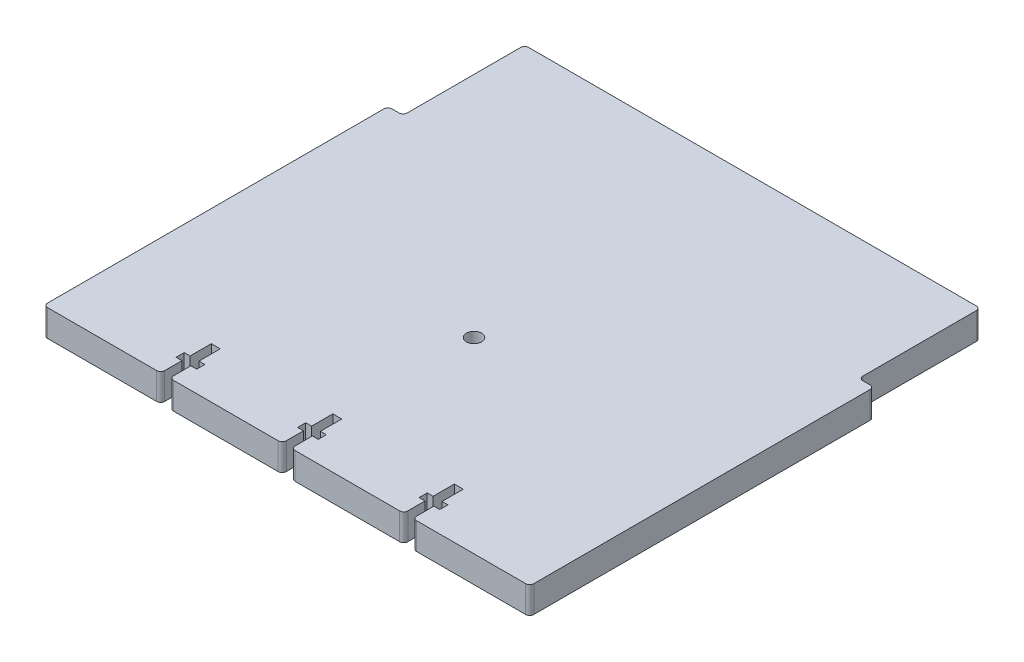
SolidWorks part; units mm, degrees
ref_plane "Front Plane" through (0, 0, 0) normal (0, 0, 1) x (1, 0, 0)
ref_plane "Top Plane" through (0, 0, 0) normal (0, 1, 0) x (1, 0, 0)
ref_plane "Right Plane" through (0, 0, 0) normal (1, 0, 0) x (0, 0, -1)
sketch "Sketch1" plane through (0, 0, 0) normal (0, 1, 0) x (1, 0, 0)
  line L1 (0, 0) -> (142.875, 0)
  line L2 (0, 107.95) -> (0, 146.05)
  line L3 (0, 146.05) -> (142.875, 146.05)
  line L4 (142.875, 107.95) -> (142.875, 146.05)
  line L5 (142.875, 0) -> (147.6375, 0)
  line L7 (142.875, 107.95) -> (147.6375, 107.95)
  line L8 (147.6375, 0) -> (147.6375, 107.95)
  line L9 (0, 0) -> (-4.7625, 0)
  line L11 (0, 107.95) -> (-4.7625, 107.95)
  line L12 (-4.7625, 0) -> (-4.7625, 107.95)
  dimension "D1" = 142.875
  dimension "D2" = 146.05
  dimension "D3" = 4.7625
  dimension "D4" = 4.7625
  dimension "D5" = 107.95
  dimension "D6" = 107.95
extrude "Boss-Extrude1" add sketch "Sketch1" along normal blind 8.382
sketch "Sketch10" plane through (0, 8.382, 0) normal (0, 1, 0) x (1, 0, 0)
  line L0 (71.4375, 146.05) -> (71.4375, 15.875) construction
  line L1 (70.0405, 9.2075) -> (68.199, 9.2075)
  line L2 (108.1405, 15.875) -> (110.9345, 15.875)
  line L3 (142.875, 146.05) -> (0, 146.05) construction
  line L4 (-4.7625, 0) -> (147.6375, 0) construction
  line L5 (70.0405, 6.6675) -> (70.0405, 0)
  line L6 (70.0405, 15.875) -> (72.8345, 15.875)
  line L7 (70.0405, 15.875) -> (70.0405, 9.2075)
  line L8 (70.0405, 0) -> (72.8345, 0)
  line L9 (72.8345, 15.875) -> (72.8345, 9.2075)
  line L10 (108.1405, 15.875) -> (108.1405, 9.2075)
  line L11 (110.9345, 15.875) -> (110.9345, 9.2075)
  line L12 (74.676, 6.6675) -> (72.8345, 6.6675)
  line L13 (74.676, 6.6675) -> (74.676, 9.2075)
  line L14 (74.676, 9.2075) -> (72.8345, 9.2075)
  line L15 (68.199, 6.6675) -> (68.199, 9.2075)
  line L16 (112.776, 9.2075) -> (110.9345, 9.2075)
  line L17 (112.776, 6.6675) -> (112.776, 9.2075)
  line L18 (70.0405, 6.6675) -> (68.199, 6.6675)
  line L19 (112.776, 6.6675) -> (110.9345, 6.6675)
  line L20 (110.9345, 6.6675) -> (110.9345, 0)
  line L21 (108.1405, 0) -> (110.9345, 0)
  line L22 (108.1405, 6.6675) -> (108.1405, 0)
  line L23 (108.1405, 6.6675) -> (106.299, 6.6675)
  line L24 (106.299, 6.6675) -> (106.299, 9.2075)
  line L25 (108.1405, 9.2075) -> (106.299, 9.2075)
  line L26 (72.8345, 6.6675) -> (72.8345, 0)
  line L27 (34.7345, 15.875) -> (34.7345, 9.2075)
  line L28 (31.9405, 15.875) -> (34.7345, 15.875)
  line L29 (31.9405, 15.875) -> (31.9405, 9.2075)
  line L30 (31.9405, 9.2075) -> (30.099, 9.2075)
  line L31 (30.099, 6.6675) -> (30.099, 9.2075)
  line L32 (31.9405, 6.6675) -> (30.099, 6.6675)
  line L33 (31.9405, 6.6675) -> (31.9405, 0)
  line L34 (34.7345, 6.6675) -> (34.7345, 0)
  line L35 (31.9405, 0) -> (34.7345, 0)
  line L36 (36.576, 6.6675) -> (34.7345, 6.6675)
  line L37 (36.576, 6.6675) -> (36.576, 9.2075)
  line L38 (36.576, 9.2075) -> (34.7345, 9.2075)
  point P6 (71.4375, 7.9375)
  point P11 (71.4375, 7.9375)
  dimension "D1" = 2.794
  dimension "D2" = 15.875
  dimension "D3" = 2.54
  dimension "D4" = 6.477
  dimension "D5" = 2
  dimension "D6" = 2
extrude "Cut-Extrude2" cut sketch "Sketch10" against normal through all
hole_wizard "3/16 (0.1875) Diameter Hole1" positions "Sketch11" profile "Sketch13" hole size "3/16" standard "ANSI Inch" end condition through all
sketch "Sketch11" plane through (0, 0, 0) normal (0, -1, 0) x (-1, 0, 0)
  line L6 (0.127, 130.175) -> (-142.875, -12.7) construction
  point P26 (-71.4375, 58.7375)
sketch "Sketch13" plane through (71.4375, 0, -58.7375) normal (1, 0, 0) x (0, 0, -1)
  line L0 (0, 0) -> (0, 8.382)
  line L1 (0, 8.382) -> (2.3812, 8.382)
  line L2 (2.3812, 8.382) -> (2.3812, 0)
  line L5 (2.3812, 0) -> (0, 0)
  line L11 (0, -6.35) -> (0, 107.95) construction
  dimension "Thru Hole Dia." = 4.7625
  dimension "Thru Hole Depth" = 8.382
fillet "Fillet1" radius 1.27 14 edges at (72.8345, 4.191, 0) (70.0405, 4.191, 0) (147.6375, 4.191, -107.95) (142.875, 4.191, -107.95) (142.875, 4.191, -146.05) (0, 4.191, -107.95) (0, 4.191, -146.05) (-4.7625, 4.191, -107.95) (-4.7625, 4.191, 0) (147.6375, 4.191, 0) (108.1405, 4.191, 0) (110.9345, 4.191, 0) (34.7345, 4.191, 0) (31.9405, 4.191, 0)
